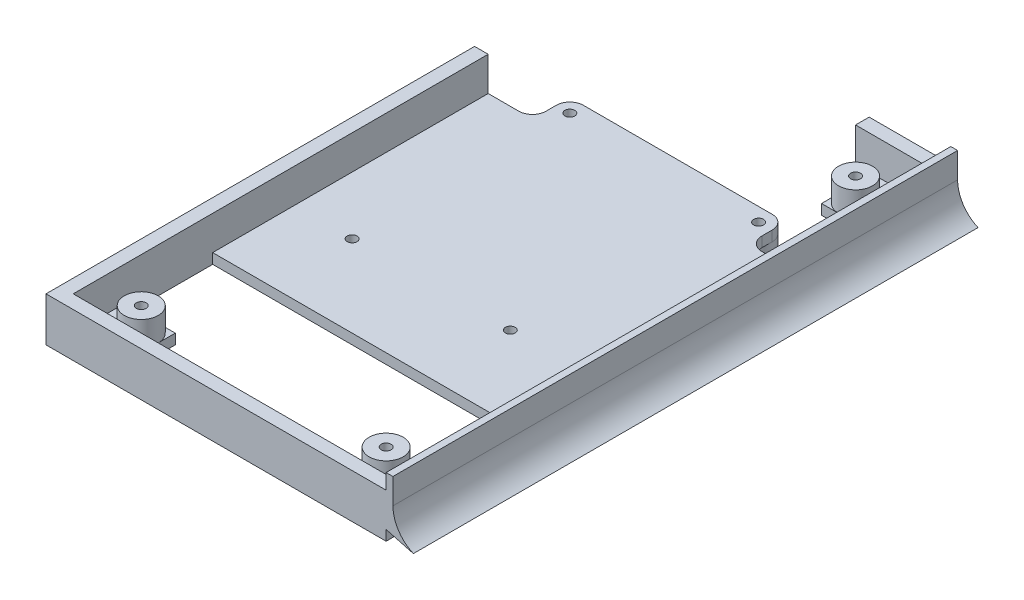
SolidWorks part; units mm, degrees
material "ABS"
ref_plane "Front Plane" through (0, 0, 0) normal (0, 0, 1) x (1, 0, 0)
ref_plane "Top Plane" through (0, 0, 0) normal (0, 1, 0) x (1, 0, 0)
ref_plane "Right Plane" through (0, 0, 0) normal (1, 0, 0) x (0, 0, -1)
sketch "Sketch1" plane through (0, 0, 0) normal (0, 1, 0) x (1, 0, 0)
  line L1 (26, 79) -> (46, 79)
  line L2 (-46, 43) -> (-46, -79)
  line L3 (-46, -79) -> (46, -79)
  line L4 (46, 79) -> (46, -79)
  line L5 (-46, 79) -> (46, -79) construction
  line L6 (-46, -79) -> (46, 79) construction
  line L10 (26, 79) -> (26, 43) construction
  line L11 (26, 43) -> (-46, 43) construction
  line L12 (26, 83) -> (50, 83)
  line L13 (50, 83) -> (50, -83)
  line L14 (-50, -83) -> (50, -83)
  line L15 (-50, 43) -> (-50, -83)
  line L16 (46, 43) -> (50, 43) construction
  line L17 (26, 79) -> (26, 83)
  line L18 (-46, 43) -> (-50, 43)
  point P0 (0, 0)
  dimension "D1" = 92
  dimension "D2" = 158
  dimension "D3" = 20
  dimension "D4" = 36
  dimension "D5" = 79
  dimension "D6" = 46
  dimension "D7" = 4
extrude "DISPLAY SUPPORT" add sketch "Sketch1" against normal blind 10 contours L2 L18 L15 L14 L13 L16 L4 L3 region at (27.9379, 0, -81)
sketch "Sketch2" plane through (0, -10, 0) normal (0, -1, 0) x (1, 0, 0)
  line L0 (50, -83) -> (50, 83) construction
  line L1 (-50, -43) -> (-33, -43)
  line L2 (-50, -43) -> (-50, 38)
  line L3 (-50, 38) -> (50, 38)
  line L4 (50, -43) -> (50, 38)
  line L5 (-33, -43) -> (-33, -54)
  line L6 (-33, -54) -> (30.5, -54)
  line L7 (30.5, -54) -> (30.5, -43)
  line L8 (30.5, -43) -> (50, -43)
  circle A2 centre (-29, 14) radius 1.45
  circle A3 centre (17.5, 14) radius 1.45
  circle A4 centre (-29, -50) radius 1.45
  circle A5 centre (26.5, -50) radius 1.45
  point P19 (0, 0)
  point P20 (0, 0)
  point P21 (0, 0)
  dimension "D5" = 2.9
  dimension "D1" = 81
  dimension "D2" = 19.5
  dimension "D3" = 17
  dimension "D4" = 11
  dimension "D6" = 21
  dimension "D7" = 24
  dimension "D8" = 67.5
  dimension "D9" = 88
  dimension "D10" = 76.5
extrude "DISPLAY DRIVER MOUNT SURFACE" add sketch "Sketch2" along normal blind 3
sketch "Sketch6" plane through (0, -10, 0) normal (0, -1, 0) x (1, 0, 0)
  line L0 (46, 38) -> (50, 38) construction
  line L1 (50, 38) -> (50, 83) construction
  line L2 (50, 83) -> (-50, 83) construction
  line L3 (-50, 83) -> (-50, 38) construction
  line L4 (-50, 38) -> (-46, 38) construction
  line L5 (-46, 38) -> (-46, 79) construction
  line L6 (-46, 79) -> (46, 79) construction
  line L7 (46, 79) -> (46, 38) construction
  line L8 (50, -43) -> (46, -43) construction
  line L9 (46, -43) -> (46, -79) construction
  line L10 (46, -79) -> (26, -79) construction
  line L11 (26, -79) -> (26, -83) construction
  line L12 (26, -83) -> (50, -83) construction
  line L13 (50, -83) -> (50, -43) construction
  line L14 (46, 38) -> (50, 38)
  line L15 (50, 38) -> (50, 83)
  line L16 (50, 83) -> (-50, 83)
  line L17 (-50, 83) -> (-50, 38)
  line L18 (-50, 38) -> (-46, 38)
  line L19 (-46, 38) -> (-46, 79)
  line L20 (-46, 79) -> (46, 79)
  line L21 (46, 79) -> (46, 38)
  line L22 (50, -43) -> (46, -43)
  line L23 (46, -43) -> (46, -79)
  line L24 (46, -79) -> (26, -79)
  line L25 (26, -79) -> (26, -83)
  line L26 (26, -83) -> (50, -83)
  line L27 (50, -83) -> (50, -43)
extrude "DISPLAY SUPPORT EXTENSION TO MATCH DRIVER MOUNT SURFACE" add sketch "Sketch6" along normal up to surface (3 mm away) up to face at (-0.625, -13, -25.5)
sketch "Sketch3" plane through (0, -13, 0) normal (0, -1, 0) x (1, 0, 0)
  circle A0 centre (-29, 14) radius 4
  circle A1 centre (17.5, 14) radius 4
  circle A2 centre (26.5, -50) radius 4
  circle A3 centre (-29, -50) radius 4
  dimension "D1" = 8
extrude "DISPLAY DRIVER POSTS" add sketch "Sketch3" along normal blind 3
fillet "Fillet1" radius 4 4 edges at (-33, -11.5, -54) (30.5, -11.5, -54) (30.5, -11.5, -43) (-33, -11.5, -43)
sketch "Sketch4" plane through (0, 0, 0) normal (0, 1, 0) x (1, 0, 0)
  line L3 (50, -83) -> (52, -83)
  line L4 (52, -83) -> (52, 83)
  line L5 (52, 83) -> (46, 83)
  line L6 (46, 83) -> (46, 43)
  line L7 (34.5, 43) -> (46, 43) construction
  line L8 (46, 43) -> (50, 43)
  line L9 (50, 43) -> (50, -83)
  point P0 (47.6361, 81.7563)
  dimension "D1" = 2
  dimension "D2" = 40
  dimension "D3" = 4
extrude "EXTENSION TO CENTER CONSOLE" add sketch "Sketch4" against normal blind 10
sketch "Sketch5" plane through (0, 0, 0) normal (0, 1, 0) x (1, 0, 0)
  line L0 (-50, -83) -> (52, -83) construction
  line L1 (52, 83) -> (50, 83)
  line L2 (52, 83) -> (52, -83)
  line L3 (52, -83) -> (50, -83)
  line L4 (50, 83) -> (50, -83)
  dimension "D1" = 2
extrude "DISPLAY EDGE LIP" add sketch "Sketch5" along normal blind 4.5
sketch "Sketch7" plane through (0, 0, 83) normal (0, 0, 1) x (1, 0, 0)
  line L0 (50, -10) -> (58, -12.1436)
  line L1 (50, -10) -> (52, -10)
  line L2 (52, -10) -> (52, -2.9784)
  line L3 (52, -10) -> (52, 4.5) construction
  arc A0 (52, -2.9784) -> (58, -12.1436) centre (62, -2.9784) ccw
  dimension "D3" = 10
  dimension "D1" = 15
  dimension "D2" = 8
extrude "DISPLAY TO CENTER CONSOLE TRIM FILLET" add sketch "Sketch7" against normal up to surface (166 mm away) up to face at (44.5, -4.625, -83)
sketch "Sketch8" plane through (0, -13, 0) normal (0, -1, 0) x (1, 0, 0)
  line L0 (-46, 79) -> (-46, 38) construction
  line L1 (50, 83) -> (31, 83)
  line L2 (50, 83) -> (50, 64)
  line L3 (50, 64) -> (31, 64)
  line L4 (31, 83) -> (31, 64)
  line L5 (-50, 83) -> (-31, 83)
  line L6 (-50, 83) -> (-50, 64)
  line L7 (-50, 64) -> (-31, 64)
  line L8 (-31, 83) -> (-31, 64)
  line L10 (50, -83) -> (31, -83)
  line L11 (50, -83) -> (50, -64)
  line L12 (50, -64) -> (31, -64)
  line L13 (31, -83) -> (31, -64)
  circle A0 centre (-36, 69) radius 1.45
  circle A1 centre (36, 69) radius 1.45
  circle A2 centre (36, -69) radius 1.45
  point P23 (0, 0)
  dimension "D4" = 2.9
  dimension "D1" = 15
  dimension "D2" = 5
  dimension "D3" = 5
  dimension "D5" = 5
  dimension "D6" = 5
extrude "USB CHG RING MOUNT POINT SURFACE" add sketch "Sketch8" against normal blind 3
sketch "Sketch9" plane through (0, -13, 0) normal (0, -1, 0) x (1, 0, 0)
  circle A0 centre (-36, 69) radius 5
  circle A1 centre (36, 69) radius 5
  circle A2 centre (-36, 69) radius 1.45 construction
  circle A3 centre (36, 69) radius 1.45 construction
  circle A4 centre (-36, 69) radius 1.45
  circle A5 centre (36, 69) radius 1.45
  circle A6 centre (36, -69) radius 1.45 construction
  circle A7 centre (36, -69) radius 1.45
  circle A8 centre (36, -69) radius 5
  dimension "D1" = 10
  dimension "D2" = 10
extrude "USB CHG RING MOUNT POSTS" add sketch "Sketch9" against normal blind 10
